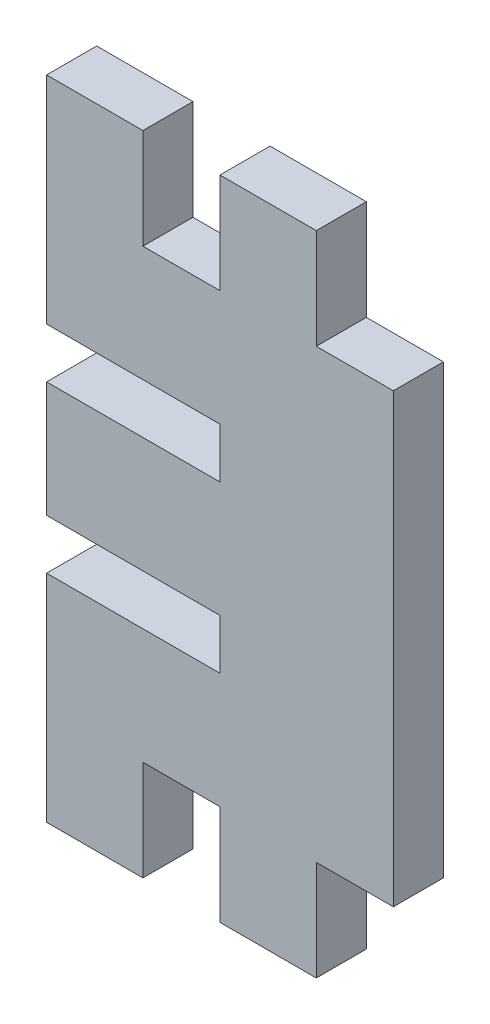
SolidWorks part; units mm, degrees
ref_plane "Front Plane" through (0, 0, 0) normal (0, 0, 1) x (1, 0, 0)
ref_plane "Top Plane" through (0, 0, 0) normal (0, 1, 0) x (1, 0, 0)
ref_plane "Right Plane" through (0, 0, 0) normal (1, 0, 0) x (0, 0, -1)
sketch "Sketch1" plane through (0, 0, 0) normal (0, 0, 1) x (1, 0, 0)
  line L0 (0, 0) -> (60.2571, 0) construction
  line L1 (55, 0) -> (-55, 0) construction
  line L2 (-18, -6) -> (-18, 6)
  line L3 (-18, 6) -> (0, 6)
  line L4 (0, 6) -> (0, 11.2)
  line L5 (0, 11.2) -> (-18, 11.2)
  line L6 (-18, 11.2) -> (-18, 33.6)
  line L7 (0, -55) -> (0, 55) construction
  line L8 (0, 1.5761) -> (0, 45.6913) construction
  line L9 (-18, 33.6) -> (-8, 33.6)
  line L10 (0, 33.6) -> (0, 23.2)
  line L11 (0, 23.2) -> (-8, 23.2)
  line L12 (-8, 23.2) -> (-8, 33.6)
  line L13 (0, 33.6) -> (10, 33.6)
  line L14 (10, 33.6) -> (10, 23.2)
  line L15 (10, 23.2) -> (18, 23.2)
  line L16 (18, 23.2) -> (18, -23.2)
  line L17 (-18, -6) -> (0, -6)
  line L18 (0, -6) -> (0, -11.2)
  line L19 (0, -11.2) -> (-18, -11.2)
  line L20 (-18, -11.2) -> (-18, -33.6)
  line L21 (0, -33.6) -> (0, -23.2)
  line L22 (-18, -33.6) -> (-8, -33.6)
  line L23 (10, -23.2) -> (18, -23.2)
  line L24 (10, -33.6) -> (10, -23.2)
  line L25 (0, -33.6) -> (10, -33.6)
  line L26 (-8, -23.2) -> (-8, -33.6)
  line L27 (0, -23.2) -> (-8, -23.2)
  line L28 (43.6365, 23.2) -> (43.537, 23.2)
  line L29 (0, -23.2) -> (0, -11.2) construction
  line L30 (0, -11.2) -> (-0.0397, -11.2018)
  point P23 (-18, 0)
  point P30 (18, 0)
  dimension "D1" = 36
  dimension "D2" = 5.2
  dimension "D3" = 10.4
  dimension "D4" = 12
  dimension "D5" = 10
  dimension "D6" = 12
  dimension "D7" = 8
extrude "Boss-Extrude2" add sketch "Sketch1" along normal blind 5.2 contours L27 L21 L25 L24 L23 L16 L15 L14 L13 L10 L11 L12 L9 L6 L5 L4 L3 L2 L17 L18 L19 L20 L22 L26 region at (0.011, 0, 0)
